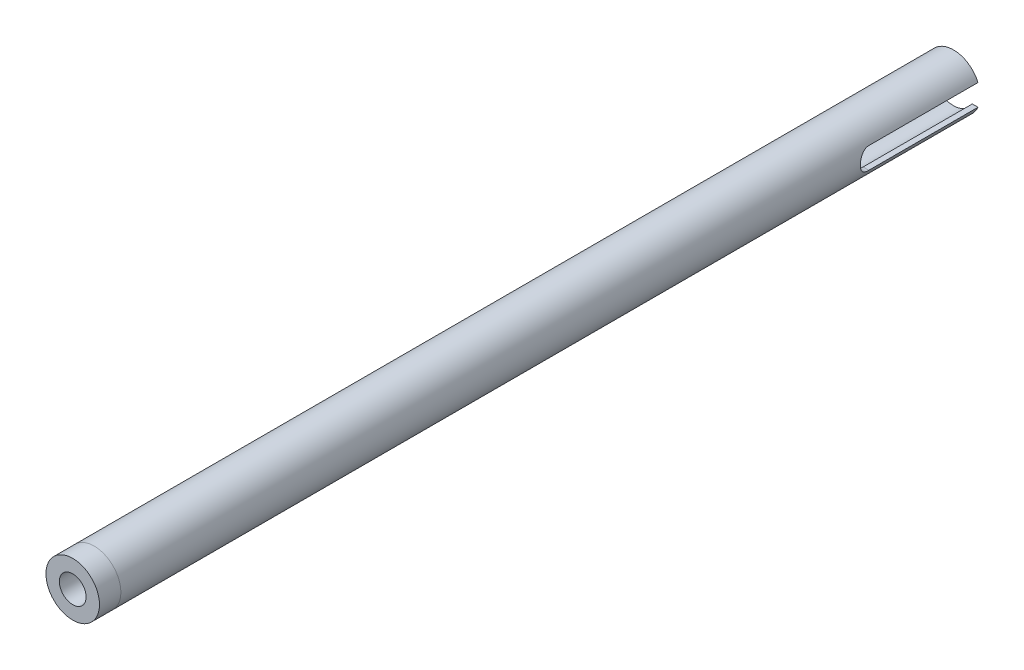
SolidWorks part; units mm, degrees
material "AISI 4130 Steel, annealed at 865C"
ref_plane "Front Plane" through (0, 0, 0) normal (0, 0, 1) x (1, 0, 0)
ref_plane "Top Plane" through (0, 0, 0) normal (0, 1, 0) x (1, 0, 0)
ref_plane "Right Plane" through (0, 0, 0) normal (1, 0, 0) x (0, 0, -1)
sketch "Axis" plane through (0, 0, 0) normal (0, 1, 0) x (1, 0, 0)
  line L0 (0, 0) -> (0, 261.2901) construction
  line L1 (0, 0) -> (0, -34.925) construction
  line L2 (0, 261.2901) -> (-7.9375, 261.2901) construction
  line L4 (0, 284.7183) -> (-10.3188, 254.2616) construction
  dimension "D1" = 34.925
  dimension "D2" = 7.9375
sketch "Sketch1" plane through (0, 0, 0) normal (0, 0, 1) x (1, 0, 0)
  line L0 (-7.9375, 0) -> (7.9375, 0) construction
  line L1 (-7.2748, 3.175) -> (7.2748, 3.175)
  line L2 (-7.2748, -3.175) -> (7.2748, -3.175)
  circle A0 centre (0, 0) radius 7.9375
  circle A1 centre (0, 0) radius 6.4135
  circle A2 centre (0, 0) radius 3.9688
  dimension "D1" = 15.875
  dimension "D3" = 7.9375
  dimension "D2" = 1.524
  dimension "D4" = 6.35
extrude "Threaded insert 1-1" add sketch "Sketch1" against normal blind 6.35 contours A2 L1 A1 | A1 L1 A0 | A2 L0 A1 L1 | A1 L0 A0 L1 | L0 A1 L2 A0 | L0 A2 L2 A1 | A2 L2 A1 | A1 L2 A0 | L0 A1 L2 A2 | L0 A0 L2 A1 | A0 L0 A1 L1 | A1 L0 A2 L1 region at (4.7887, 1.6543, 0) region at (4.7887, -1.6543, 0) region at (6.9234, 1.6163, 0) region at (6.9234, -1.6163, 0) region at (-4.7887, -1.6543, 0) region at (-4.7887, 1.6543, 0) region at (0, 4.6159, 0) region at (0, -4.6159, 0) region at (0, 6.5666, 0) region at (6.4237, -3.3281, 0) region at (-6.9234, -1.6163, 0) region at (-6.9234, 1.6163, 0)
extrude "Threaded insert 1-2" add sketch "Sketch1<3>" against normal blind 9.525 from surface contours A2 L1 A1 | A2 L0 A1 L1 | L0 A2 L2 A1 | A2 L2 A1 | L0 A1 L2 A2 | A1 L0 A2 L1 region at (4.7887, 1.6543, 0) region at (4.7887, -1.6543, 0) region at (-4.7887, -1.6543, 0) region at (-4.7887, 1.6543, 0) region at (0, 4.6159, 0) region at (0, -4.6159, 0) starting at face at (7.9375, 0, -6.35)
sketch "Sketch1<3>" plane through (0, 0, 0) normal (0, 0, 1) x (1, 0, 0) same geometry as "Sketch1"
extrude "A-arm tube" add sketch "Sketch1<4>" against normal up to vertex (261.2901 mm away) from surface separate body contours A1 L1 A0 | A1 L0 A0 L1 | L0 A1 L2 A0 | A1 L2 A0 | L0 A0 L2 A1 | A0 L0 A1 L1 region at (6.9234, 1.6163, 0) region at (6.9234, -1.6163, 0) region at (0, 6.5666, 0) region at (6.4237, -3.3281, 0) region at (-6.9234, -1.6163, 0) region at (-6.9234, 1.6163, 0) up to point (0, 0, -261.2901) starting at face at (6.4135, 0, -6.35)
sketch "Sketch1<4>" plane through (0, 0, 0) normal (0, 0, 1) x (1, 0, 0) same geometry as "Sketch1"
extrude "Apex slot" cut sketch "Sketch1<5>" along normal blind 35.56 from surface contours A0 L0 A1 L1 | L0 A0 L2 A1 | A1 L0 A0 L1 | L0 A1 L2 A0 region at (6.9234, 1.6163, 0) region at (6.9234, -1.6163, 0) region at (-6.9234, -1.6163, 0) region at (-6.9234, 1.6163, 0) starting at face at (6.4135, 0, -261.2901)
sketch "Sketch1<5>" plane through (0, 0, 0) normal (0, 0, 1) x (1, 0, 0) same geometry as "Sketch1"
fillet "Fillet1" radius 3.175 4 edges at (-6.4237, 3.175, -225.7301) (-6.4237, -3.175, -225.7301) (6.4237, -3.175, -225.7301) (6.4237, 3.175, -225.7301)
equation "\"tube diameter\"= 5 / 8"
equation "\"tube thickness\"= .06"
equation "\"apex thickness\"= .25"
equation "\"tube slot\"= 1.4"
equation "\"D1@Sketch1\"=\"tube diameter\""
equation "\"D2@Sketch1\"=\"tube thickness\""
equation "\"threaded insert hole\"= .3125"
equation "\"D3@Sketch1\"=\"threaded insert hole\""
equation "\"D4@Sketch1\"=\"apex thickness\""
equation "\"D1@Apex slot\" = \"tube slot\""
equation "\"D1@Fillet1\"=\"apex thickness\"/2"
